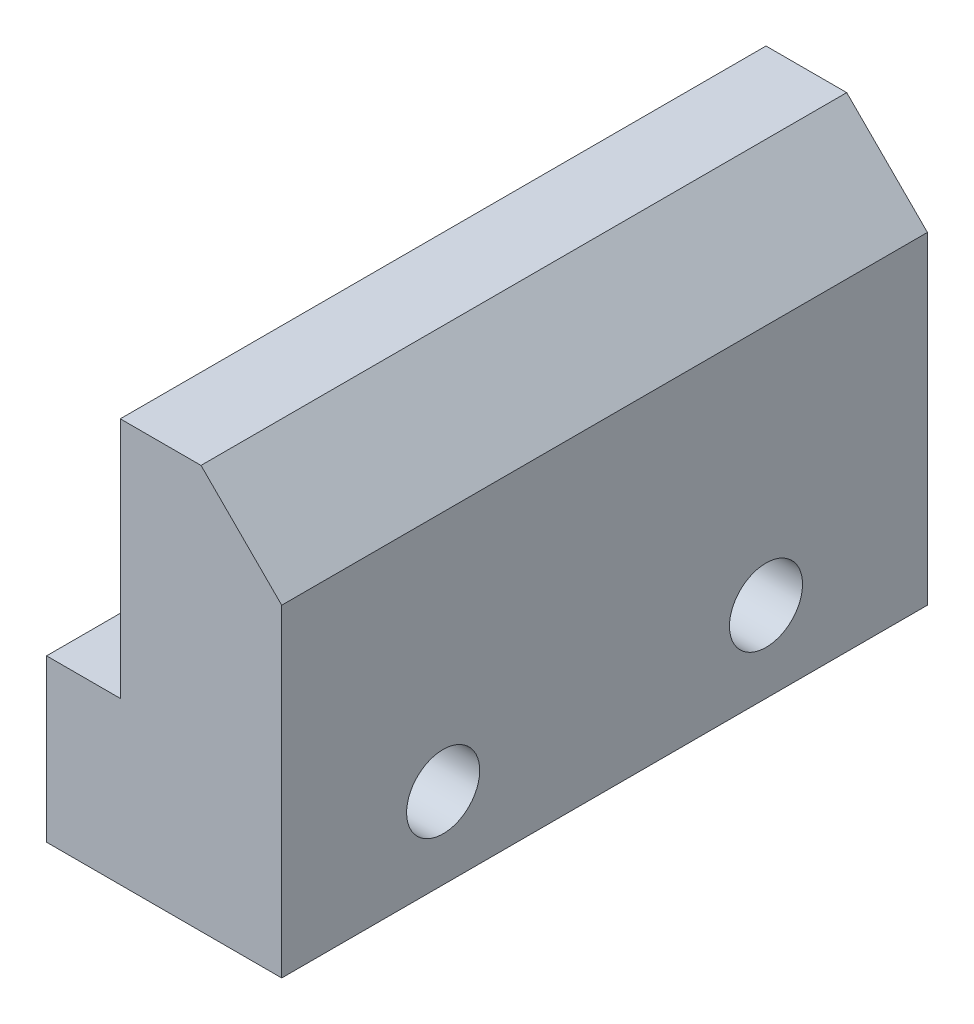
SolidWorks part; units mm, degrees
material "PETG"
ref_plane "Front Plane" through (0, 0, 0) normal (0, 0, 1) x (1, 0, 0)
ref_plane "Top Plane" through (0, 0, 0) normal (0, 1, 0) x (1, 0, 0)
ref_plane "Right Plane" through (0, 0, 0) normal (1, 0, 0) x (0, 0, -1)
sketch "Sketch1" plane through (0, 0, 0) normal (0, 0, 1) x (1, 0, 0)
  line L0 (11.6, 63.5) -> (37, 38.1)
  line L1 (0, -12.7) -> (37, -12.7)
  line L2 (0, -12.7) -> (0, 12.7)
  line L3 (0, 12.7) -> (11.6, 12.7)
  line L6 (11.6, 63.5) -> (11.6, 12.7)
  line L8 (37, 38.1) -> (37, -12.7)
  line L9 (11.6, 50.8) -> (24.3, 50.8)
  dimension "D1" = 25.4
  dimension "D2" = 37
  dimension "D3" = 50.8
  dimension "D4" = 25.4
  dimension "D5" = 25.4
extrude "Boss-Extrude1" add sketch "Sketch1" along normal mid plane 101.6 contours L9 L6 L3 L2 L1 L8 L0 region at (20.9426, 14.763, 0)
sketch "Sketch2" plane through (37, 0, 0) normal (1, 0, 0) x (0, 0, -1)
  line L0 (-25.4, 0) -> (0, 0) construction
  line L1 (0, 0) -> (25.4, 0) construction
  line L2 (-50.8, 38.1) -> (-50.8, -12.7) construction
  circle A0 centre (-25.4, 0) radius 3.25
  circle A1 centre (25.4, 0) radius 3.25
  dimension "D1" = 25.4
  dimension "D2" = 6.5
extrude "Cut-Extrude1" cut sketch "Sketch2" against normal through all
sketch "Sketch3" plane through (37, 0, 0) normal (1, 0, 0) x (0, 0, -1)
  circle A0 centre (-25.4, 0) radius 5.75
  circle A1 centre (25.4, 0) radius 5.75
  dimension "D1" = 11.5
extrude "Cut-Extrude2" cut sketch "Sketch3" against normal offset from surface (27 mm away) 10 up to face at (0, 3.25, 25.4)
equation "\"D2@Sketch1\"=37mm"
